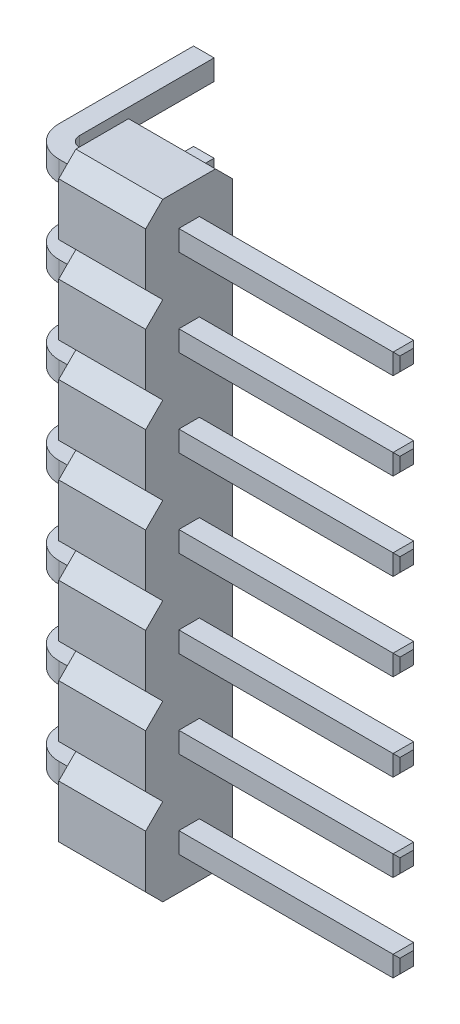
SolidWorks part; units mm, degrees
ref_plane "Front Plane" through (0, 0, 0) normal (0, 0, 1) x (1, 0, 0)
ref_plane "Top Plane" through (0, 0, 0) normal (0, 1, 0) x (1, 0, 0)
ref_plane "Right Plane" through (0, 0, 0) normal (1, 0, 0) x (0, 0, -1)
sketch "Sketch1" plane through (0, 0, 0) normal (1, 0, 0) x (0, 0, -1)
  line L0 (0, 0) -> (-1.27, 0) construction
  line L5 (-1.27, 0) -> (-1.27, 1.27) construction
  line L6 (-2.04, 1.27) -> (-0.5, 1.27)
  line L7 (-0.5, 1.27) -> (0, 0.77)
  line L8 (0, 0.77) -> (0, -0.77)
  line L9 (-2.54, 0.77) -> (-2.54, -0.77)
  line L10 (-2.04, 1.27) -> (-2.54, 0.77)
  line L11 (-0.5, -1.27) -> (0, -0.77)
  line L12 (-2.04, -1.27) -> (-0.5, -1.27)
  line L13 (-2.04, -1.27) -> (-2.54, -0.77)
  point P13 (-2.54, 0)
  dimension "D1" = 1.27
  dimension "D2" = 45
  dimension "D3" = 0.5
extrude "Plastic" add sketch "Sketch1" along normal blind 2.54
sketch "Sketch2" plane through (0, 0, 0) normal (0, 1, 0) x (1, 0, 0)
  line L0 (-1.56, 3.36) -> (-1.56, -0.67) construction
  line L1 (-0.96, -1.27) -> (8.9, -1.27) construction
  line L2 (0, -2.04) -> (0, -0.5) construction
  line L3 (-1.86, 3.36) -> (-1.86, -0.67)
  line L4 (-0.96, -1.57) -> (8.9, -1.57)
  line L5 (-1.26, 3.36) -> (-1.26, -0.67)
  line L6 (-0.96, -0.97) -> (8.9, -0.97)
  line L7 (-1.86, 3.36) -> (-1.26, 3.36)
  line L8 (8.9, -1.57) -> (8.9, -0.97)
  line L9 (2.54, -2.54) -> (0, -2.54) construction
  line L10 (2.54, -2.04) -> (2.54, -0.5) construction
  arc A0 (-1.56, -0.67) -> (-0.96, -1.27) centre (-0.96, -0.67) ccw construction
  arc A1 (-1.86, -0.67) -> (-0.96, -1.57) centre (-0.96, -0.67) ccw
  arc A2 (-1.26, -0.67) -> (-0.96, -0.97) centre (-0.96, -0.67) ccw
  point P5 (0, -1.27)
  dimension "D1" = 0.6
  dimension "D4" = 8.9
  dimension "D5" = 5.9
  dimension "D6" = 4.4
  dimension "D2" = 0.3
  dimension "D3" = 0.3
extrude "Contact" add sketch "Sketch2" along normal mid plane 0.6
chamfer "Chamfer1" distance 0.1 angle 45 8 edges at (8.9, 0.3, 1.27) (8.9, 0, 1.57) (8.9, -0.3, 1.27) (8.9, 0, 0.97) (-1.56, 0.3, -3.36) (-1.26, 0, -3.36) (-1.86, 0, -3.36) (-1.56, -0.3, -3.36)
pattern_linear "LPattern1" count 7 spacing 2.54 along (0, 1, 0) of "Plastic", "Contact", "Chamfer1"
sketch "Sketch3" plane through (0, 0, -3.36) normal (0, 0, -1) x (-1, 0, 0)
  line L0 (1.36, 0) -> (1.56, 0) construction
  line L1 (1.36, 0.2) -> (1.36, -0.2) construction
  line L2 (1.56, 0) -> (1.56, -0.2) construction
  line L3 (1.36, -0.2) -> (1.76, -0.2) construction
ref_axis "Axis1" through (-1.56, 0, -3.36) along (0, 0, 1)
ref_plane "Plane1" through (0, 7.62, 0) normal (0, 1, 0) x (1, 0, 0)
